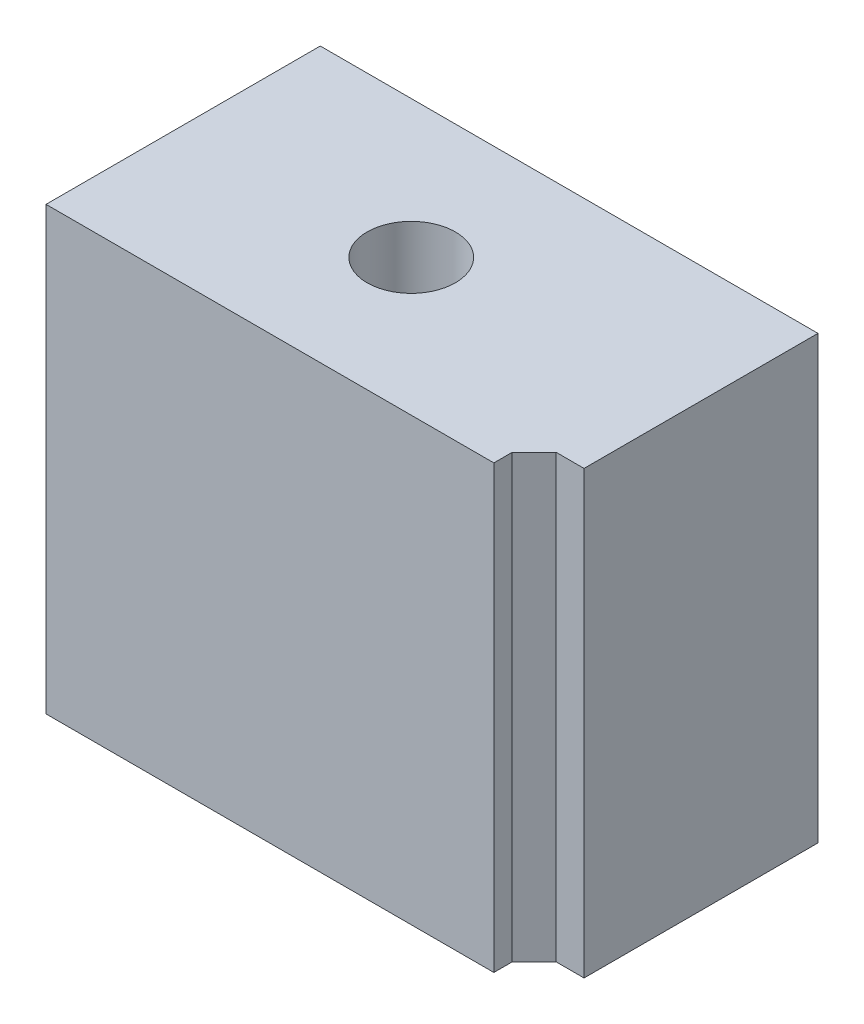
SolidWorks part; units mm, degrees
ref_plane "Front Plane" through (0, 0, 0) normal (0, 0, 1) x (1, 0, 0)
ref_plane "Top Plane" through (0, 0, 0) normal (0, 1, 0) x (1, 0, 0)
ref_plane "Right Plane" through (0, 0, 0) normal (1, 0, 0) x (0, 0, -1)
sketch "Sketch3" plane through (0, 0, 0) normal (0, 1, 0) x (1, 0, 0)
  line L0 (-51.7846, 31.1667) -> (-51.7846, -30.9749)
  line L1 (-51.7846, -30.9749) -> (60.9908, -30.9749)
  line L2 (60.9908, -30.9749) -> (60.9908, 31.1667)
  line L3 (60.9908, 31.1667) -> (-51.7846, 31.1667)
extrude "Boss-Extrude1" add sketch "Sketch3" along normal blind 100
sketch "Sketch4" plane through (0, 100, 0) normal (0, 1, 0) x (1, 0, 0)
  line L0 (60.9908, -21.8401) -> (49.6904, -21.8401)
  line L1 (60.9908, -30.9749) -> (60.9908, 31.1667) construction
  line L2 (49.6904, -21.8401) -> (49.6904, -30.9749)
  line L3 (-51.7846, -30.9749) -> (60.9908, -30.9749) construction
  line L4 (49.6904, -30.9749) -> (60.9908, -30.9749)
  line L5 (60.9908, -30.9749) -> (60.9908, -21.8401)
extrude "Cut-Extrude1" cut sketch "Sketch4" against normal blind 100 contours L5 L0 L2 L4
fillet "Chamfer2" radius 5 1 edges at (49.6904, 50, 21.8401) type face fillet profile chamfer first side face at (55.3406, 50, 21.8401) second side face at (49.6904, 50, 26.4075)
sketch "Sketch5" plane through (0, 100, 0) normal (0, 1, 0) x (1, 0, 0)
  circle A0 centre (0, 0) radius 10
extrude "Cut-Extrude2" cut sketch "Sketch5" against normal blind 100 contours A0
